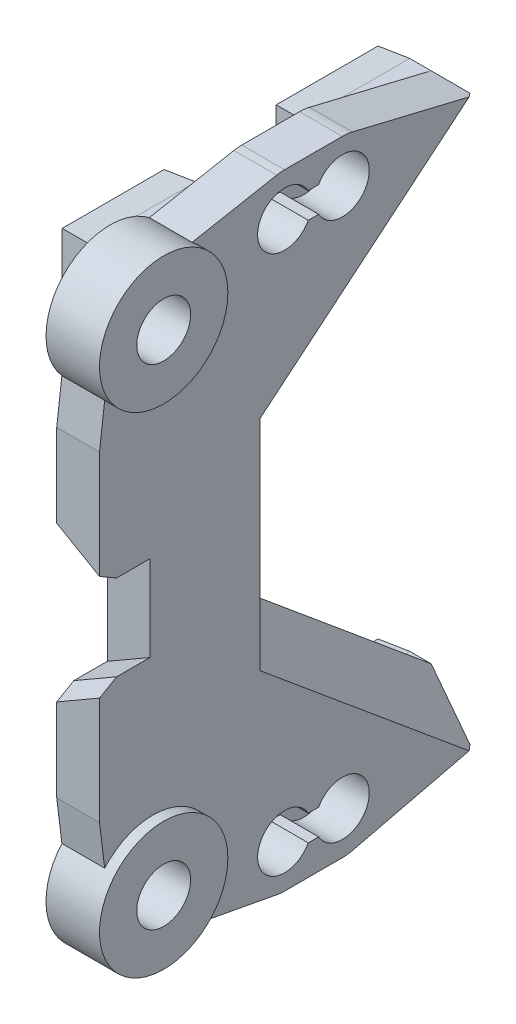
SolidWorks part; units mm, degrees
note: The reader was unsure of these and kept them because the rebuilt part matched: shared geometry of "Sketch11<2>".
ref_plane "Front Plane" through (0, 0, 0) normal (0, 0, 1) x (1, 0, 0)
ref_plane "Top Plane" through (0, 0, 0) normal (0, 1, 0) x (1, 0, 0)
ref_plane "Right Plane" through (0, 0, 0) normal (1, 0, 0) x (0, 0, -1)
sketch "SlideGeometry"
  dimension "D1" = 38.1
  dimension "D2" = 12.7
  dimension "D3" = 25.4
  dimension "D4" = 50.8
  dimension "D6" = 12.7
  dimension "D7" = 6.35
  dimension "D8" = 6.35
  dimension "D9" = 12.7
  dimension "D12" = 3.81
  dimension "D5" = 9.525
  dimension "D10" = 12.7
  dimension "D11" = 3.81
sketch_block_instance "PulleyOutline-1"
sketch_block "PulleyOutline" parameters "D1"=11.1125, "D2"=13.6525
sketch_block_instance "PulleyOutline-2"
sketch_block_instance "PulleyOutline-3"
sketch_block_instance "PulleyOutline-4"
sketch_block_instance "PulleyOutline-5"
sketch_block_instance "PulleyOutline-6"
sketch_block_instance "SlotOutline-1"
sketch_block "SlotOutline" parameters "D1"=6.35, "D2"=3
sketch_block_instance "SlotOutline-3"
sketch_block_instance "SlotOutline-4"
sketch "Sketch3" plane through (0, 0, 0) normal (1, 0, 0) x (0, 0, -1)
  circle A0 centre (-3.175, 14.5337) radius 3.81
  circle A1 centre (-3.175, 14.5337) radius 1.5 construction
  dimension "D1" = 7.62
  dimension "D2" = 3
extrude "DowelSupport" add sketch "Sketch3" along normal blind 1.905 and the other way blind 1.27
sketch "Sketch5" plane through (0, 0, 0) normal (1, 0, 0) x (0, 0, -1)
  line L1 (-6.35, -9.525) -> (3.175, -9.525)
  line L2 (-6.35, -9.525) -> (-6.35, 9.525)
  line L3 (-6.35, 9.525) -> (3.175, 9.525)
  line L4 (3.175, -9.525) -> (3.175, 9.525)
  line L5 (-6.35, -9.525) -> (3.175, 9.525) construction
  line L6 (-6.35, 9.525) -> (3.175, -9.525) construction
  point P0 (-1.5875, 0)
  dimension "D1" = 9.525
  dimension "D2" = 19.05
  dimension "D3" = 3.175
extrude "SliderDowelSupport" add sketch "Sketch5" along normal mid plane 2.54 separate body contours L3 L4 L1 L2
sketch "Sketch8" plane through (0, 0, 0) normal (1, 0, 0) x (0, 0, -1)
  line L0 (4.6355, 16.002) -> (8.0645, 16.002) construction
  line L1 (4.6355, 18.542) -> (8.0645, 18.542)
  line L2 (4.6355, 13.462) -> (8.0645, 13.462)
  line L3 (6.35, 19.05) -> (-6.35, 19.05) construction
  circle A0 centre (4.6355, 16.002) radius 1.5 construction
  circle A1 centre (8.0645, 16.002) radius 1.5 construction
  arc A2 (4.6355, 18.542) -> (4.6355, 13.462) centre (4.6355, 16.002) ccw
  arc A3 (5.7373, 17.0198) -> (5.5245, 16.002) centre (8.0645, 16.002) ccw construction
  arc A4 (8.0645, 18.542) -> (6.35, 17.8761) centre (8.0645, 16.002) ccw construction
  arc A5 (6.35, 17.8761) -> (4.6355, 18.542) centre (4.6355, 16.002) ccw construction
  arc A6 (6.35, 17.8761) -> (5.7373, 17.0198) centre (8.0645, 16.002) ccw construction
  arc A7 (6.9627, 17.0198) -> (6.35, 17.8761) centre (4.6355, 16.002) ccw construction
  arc A8 (7.1755, 16.002) -> (6.9627, 17.0198) centre (4.6355, 16.002) ccw construction
  arc A9 (6.9627, 14.9842) -> (7.1755, 16.002) centre (4.6355, 16.002) ccw construction
  arc A10 (6.35, 14.1279) -> (6.9627, 14.9842) centre (4.6355, 16.002) ccw construction
  arc A11 (5.7373, 14.9842) -> (6.35, 14.1279) centre (8.0645, 16.002) ccw construction
  arc A12 (8.0645, 13.462) -> (8.0645, 18.542) centre (8.0645, 16.002) ccw
  arc A13 (4.6355, 13.462) -> (6.35, 14.1279) centre (4.6355, 16.002) ccw construction
  arc A14 (6.35, 14.1279) -> (8.0645, 13.462) centre (8.0645, 16.002) ccw construction
  arc A15 (5.5245, 16.002) -> (5.7373, 14.9842) centre (8.0645, 16.002) ccw construction
  point P11 (6.35, 16.002)
  dimension "D1" = 3
  dimension "D3" = 5.08
  dimension "D2" = 3.429
  dimension "D4" = 0.508
  dimension "D5" = 9.525
extrude "StringDowelSupport" add sketch "Sketch8" along normal mid plane 2.54 separate body
sketch "Sketch9" plane through (0, 0, 0) normal (1, 0, 0) x (0, 0, -1)
  line B0 (3.175, 13.74) -> (-3.175, 13.74)
  line B1 (3.175, 13.74) -> (3.175, 16.74)
  line B2 (3.175, 16.74) -> (-3.175, 16.74)
  line B3 (-3.175, 13.74) -> (-3.175, 16.74)
  line B4 (3.175, 13.74) -> (-3.175, 16.74) construction
  line B5 (3.175, 16.74) -> (-3.175, 13.74) construction
  line B6 (15.875, 13.74) -> (9.525, 13.74)
  line B7 (15.875, 13.74) -> (15.875, 16.74)
  line B8 (15.875, 16.74) -> (9.525, 16.74)
  line B9 (9.525, 13.74) -> (9.525, 16.74)
sketch_block_instance "3DPTabGeo-1"
sketch_block "3DPTabGeo" parameters "D1"=3, "D2"=6.35
sketch_block_instance "3DPTabGeo-2"
extrude "TabSupport" add sketch "Sketch9" along normal mid plane 2.54
sketch "Sketch10" plane through (0, 0, 0) normal (1, 0, 0) x (0, 0, -1)
  line L0 (-6.35, 9.525) -> (-5.696, 14.8437)
  line L1 (-5.696, 14.8437) -> (-0.654, 14.2238) construction
  line L2 (-6.35, 9.525) -> (3.175, 9.525)
  line L3 (3.175, 9.525) -> (3.175, 3.175)
  line L4 (3.175, 3.175) -> (15.875, 13.74)
  line L5 (15.875, 13.74) -> (15.875, 16.74)
  line L6 (15.875, 16.74) -> (8.6571, 18.4719)
  line L7 (8.6571, 18.4719) -> (4.1662, 18.4983)
  line L8 (4.1662, 18.4983) -> (-3.6443, 17.03)
  line L9 (-3.6443, 17.03) -> (-2.7057, 12.0375) construction
  line L10 (-5.696, 14.8437) -> (-3.6443, 17.03)
  line L11 (3.175, -9.525) -> (3.175, 9.525) construction
  arc A0 (4.6355, 18.542) -> (4.6355, 13.462) centre (4.6355, 16.002) ccw construction
  arc A1 (8.0645, 13.462) -> (8.0645, 18.542) centre (8.0645, 16.002) ccw construction
  point P3 (-3.175, 14.5337)
  dimension "D1" = 5.08
  dimension "D2" = 6.35
extrude "InterSupport" add sketch "Sketch10" along normal mid plane 2.54
sketch "Sketch11" plane through (0, 0, 0) normal (1, 0, 0) x (0, 0, -1)
  line L1 (6.0424, 15.24) -> (6.6576, 15.24)
  line L2 (6.0424, 15.24) -> (6.0424, 16.764) construction
  line L3 (6.0424, 16.764) -> (6.6576, 16.764)
  line L4 (6.6576, 15.24) -> (6.6576, 16.764) construction
  line L5 (6.0424, 15.24) -> (6.6576, 16.764) construction
  line L6 (6.0424, 16.764) -> (6.6576, 15.24) construction
  circle A0 centre (-3.175, 14.5337) radius 1.6
  arc A1 (6.0424, 16.764) -> (6.0424, 15.24) centre (4.6355, 16.002) ccw
  arc A2 (6.6576, 15.24) -> (6.6576, 16.764) centre (8.0645, 16.002) ccw
  arc A3 (6.1771, 16.4303) -> (6.0424, 16.764) centre (4.6355, 16.002) ccw construction
  arc A4 (6.6576, 16.764) -> (6.5229, 16.4303) centre (8.0645, 16.002) ccw construction
  arc A5 (6.5229, 16.4303) -> (6.5229, 15.5737) centre (8.0645, 16.002) ccw construction
  arc A6 (6.1771, 15.5737) -> (6.1771, 16.4303) centre (4.6355, 16.002) ccw construction
  arc A7 (6.0424, 15.24) -> (6.1771, 15.5737) centre (4.6355, 16.002) ccw construction
  arc A8 (6.5229, 15.5737) -> (6.6576, 15.24) centre (8.0645, 16.002) ccw construction
  point P9 (6.35, 16.002)
  dimension "D3" = 1.524
extrude "DowelHoles" cut sketch "Sketch11" against normal through all both and the other way through all
extrude "Boss-Extrude1" add sketch "Sketch11<2>" along normal blind 0.254 from surface contours L1 A2 L3 A1 | A0
sketch "Sketch11<2>" plane through (0, 0, 0) normal (1, 0, 0) x (0, 0, -1) same geometry as "Sketch11"
sketch "Sketch14" plane through (-1.27, 0, 0) normal (-1, 0, 0) x (0, 0, 1)
  line B0 (-9.525, 13.74) -> (-15.875, 13.74)
  line B1 (-9.525, 13.74) -> (-9.525, 16.74)
  line B2 (-9.525, 16.74) -> (-15.875, 16.74)
  line B3 (-15.875, 13.74) -> (-15.875, 16.74)
  line B4 (-9.525, 16.74) -> (-15.875, 13.74) construction
  line B5 (3.175, 13.74) -> (-3.175, 13.74)
  line B6 (3.175, 13.74) -> (3.175, 16.74)
  line B7 (3.175, 16.74) -> (-3.175, 16.74)
  line B8 (-3.175, 13.74) -> (-3.175, 16.74)
sketch_block_instance "3DPTabGeo-3"
sketch_block_instance "3DPTabGeo-4"
extrude "TabBase" add sketch "Sketch14" along normal blind 1.27
sketch "Sketch15" plane through (-2.54, 0, 0) normal (-1, 0, 0) x (0, 0, 1)
  line L0 (-3.175, 16.74) -> (-3.175, 13.74) construction
  line L1 (-3.175, 13.74) -> (3.175, 13.74) construction
  line L2 (3.175, 13.74) -> (3.175, 16.74) construction
  line L3 (3.175, 16.74) -> (-3.175, 16.74) construction
  line L4 (-15.875, 16.74) -> (-15.875, 13.74) construction
  line L5 (-15.875, 13.74) -> (-9.525, 13.74) construction
  line L6 (-9.525, 13.74) -> (-9.525, 16.74) construction
  line L7 (-9.525, 16.74) -> (-15.875, 16.74) construction
  line L8 (-3.175, 16.74) -> (-3.175, 13.74)
  line L9 (-3.175, 13.74) -> (3.175, 13.74)
  line L10 (3.175, 13.74) -> (3.175, 16.74)
  line L11 (3.175, 16.74) -> (-3.175, 16.74)
  line L12 (-15.875, 16.74) -> (-15.875, 13.74)
  line L13 (-15.875, 13.74) -> (-9.525, 13.74)
  line L14 (-9.525, 13.74) -> (-9.525, 16.74)
  line L15 (-9.525, 16.74) -> (-15.875, 16.74)
extrude "TabDraft" add sketch "Sketch15" along normal offset from surface 3 draft 5
chamfer "Chamfer1" distance 2.54 angle 45 1 edges at (1.27, 8.4575, -9.525)
mirror "Mirror1" about plane through (0, 0, 0) normal (0, 1, 0) of bodies 118 115
sketch "Sketch17" plane through (0, 0, 6.35) normal (0, 0, 1) x (1, 0, 0)
  line L0 (-1.27, -4.0065) -> (1.27, -2.54)
  line L1 (-1.27, -9.525) -> (-1.27, 9.525) construction
  line L2 (1.27, -9.525) -> (1.27, 9.525) construction
  line L3 (1.27, -2.54) -> (1.27, 2.54)
  line L4 (1.27, 2.54) -> (-1.27, 4.0065)
  line L5 (-1.27, 4.0065) -> (-1.27, -4.0065)
  line L6 (0, 0) -> (2.5247, 0) construction
  dimension "D1" = 60
  dimension "D2" = 5.08
extrude "Cut-Extrude2" cut sketch "Sketch17" against normal blind 3
chamfer "Chamfer2" distance 0.508 distance2 1.016 2 edges at (0, -3.2732, 6.35) (0, 3.2732, 6.35)
equation "\"StageWidth\"= 1.5"
equation "\"D1@SlideGeometry\" = \"StageWidth\""
equation "\"StageOffset\"= .5in"
equation "\"D3@SlideGeometry\" = \"StageWidth\" - \"StageOffset\""
equation "\"D4@SlideGeometry\" = \"StageWidth\" + \"StageOffset\""
equation "\"SlideOffset\"= 0.5in"
equation "\"D6@SlideGeometry\" = \"SlideOffset\""
equation "\"D7@SlideGeometry\" = \"StageOffset\" / 2"
equation "\"D8@SlideGeometry\" = \"StageOffset\" / 2"
equation "\"D9@SlideGeometry\" = \"SlideOffset\""
equation "\"OuterThickness\"= 0.1in"
equation "\"D1@SliderDowelSupport\"=\"OuterThickness\""
equation "\"D1@DowelSupport\"=\"OuterThickness\"/2+.025in"
equation "\"DowelClearance\"= 3mm + .2mm"
equation "\"D1@TabSupport\" = \"OuterThickness\""
equation "\"D1@InterSupport\" = \"OuterThickness\""
equation "\"D1@Sketch11\"=\"DowelClearance\""
equation "\"D2@Sketch11\"=\"DowelClearance\""
equation "\"SliderDowelLength\"= .5in"
equation "\"D2@Sketch5\"=\"SliderDowelLength\"+.25in"
equation "\"D11@SlideGeometry\"=\"D12@SlideGeometry\""
equation "\"D2@DowelSupport\"=\"OuterThickness\"/2"
